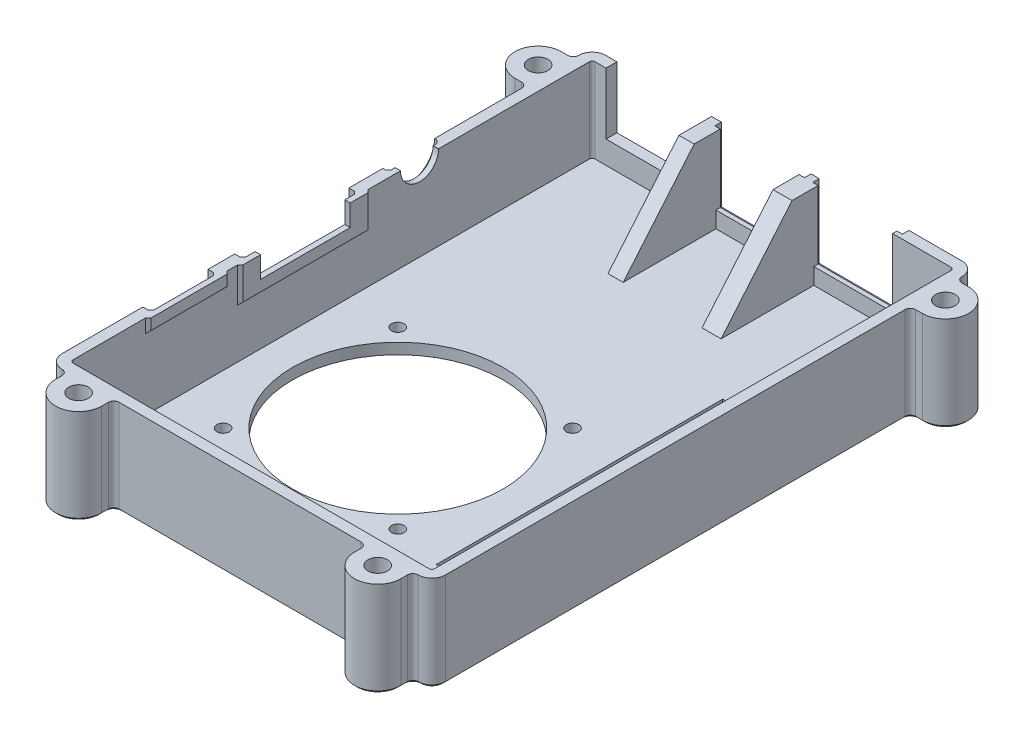
SolidWorks part; units mm, degrees
ref_plane "Front Plane" through (0, 0, 0) normal (0, 0, 1) x (1, 0, 0)
ref_plane "Top Plane" through (0, 0, 0) normal (0, 1, 0) x (1, 0, 0)
ref_plane "Right Plane" through (0, 0, 0) normal (1, 0, 0) x (0, 0, -1)
sketch "Sketch2" plane through (0, 0, 0) normal (0, 1, 0) x (1, 0, 0)
  line L1 (2.5, 0) -> (68, 0)
  line L2 (0, 2.5) -> (0, 97.5)
  line L3 (2.5, 100) -> (68, 100)
  line L4 (70.5, 2.5) -> (70.5, 97.5)
  arc A0 (0, 2.5) -> (2.5, 0) centre (2.5, 2.5) ccw
  arc A1 (68, 0) -> (70.5, 2.5) centre (68, 2.5) ccw
  arc A2 (70.5, 97.5) -> (68, 100) centre (68, 97.5) ccw
  arc A3 (2.5, 100) -> (0, 97.5) centre (2.5, 97.5) ccw
  point P7 (0, 0)
  point P10 (70.5, 0)
  point P13 (70.5, 100)
  point P16 (0, 100)
  dimension "D3" = 2.5
  dimension "D1" = 70.5
  dimension "D2" = 100
extrude "Base" add sketch "Sketch2" along normal blind 17.5
shell "Shell" thickness 2 removed face at (35.25, 17.5, -50)
sketch "Sketch14" plane through (0, 0, 0) normal (0, -1, 0) x (1, 0, 0)
  line L0 (35.25, 0) -> (35.25, -100) construction
  line L2 (68, -100) -> (2.5, -100) construction
  line L3 (-2.2, -88) -> (0, -88)
  line L4 (0, -97.5) -> (0, -2.5) construction
  line L5 (0, -88) -> (0, -96.5)
  line L6 (0, -96.5) -> (-2.2, -96.5)
  line L7 (3.5, 2.2) -> (3.5, 0)
  line L8 (2.5, 0) -> (68, 0) construction
  line L9 (3.5, 0) -> (12, 0)
  line L10 (12, 0) -> (12, 2.2)
  line L11 (72.7, -88) -> (70.5, -88)
  line L12 (70.5, -96.5) -> (72.7, -96.5)
  line L13 (70.5, -88) -> (70.5, -96.5)
  line L14 (58.5, 0) -> (58.5, 2.2)
  line L15 (67, 0) -> (58.5, 0)
  line L16 (67, 2.2) -> (67, 0)
  line L17 (2.5, 0) -> (68, 0) construction
  arc A0 (-2.2, -88) -> (-2.2, -96.5) centre (-2.2, -92.25) ccw
  arc A1 (3.5, 2.2) -> (12, 2.2) centre (7.75, 2.2) cw
  arc A2 (72.7, -88) -> (72.7, -96.5) centre (72.7, -92.25) cw
  arc A3 (67, 2.2) -> (58.5, 2.2) centre (62.75, 2.2) ccw
  dimension "D1" = 2.2
  dimension "D2" = 8.5
  dimension "D3" = 3.5
  dimension "D4" = 3.5
extrude "Clamps" add sketch "Sketch14" against normal up to surface (17.5 mm away) up to face at (35.25, 17.5, -50)
fillet "Clamp Fillets" radius 1 8 edges at (58.5, 8.75, 0) (67, 8.75, 0) (12, 8.75, 0) (3.5, 8.75, 0) (0, 8.75, -96.5) (0, 8.75, -88) (70.5, 8.75, -88) (70.5, 8.75, -96.5)
sketch "Sketch20" plane through (0, 0, 0) normal (0, -1, 0) x (1, 0, 0)
  circle A0 centre (7.75, 2.2) radius 1.8
  circle A1 centre (62.75, 2.2) radius 1.8
  circle A2 centre (72.7, -92.25) radius 1.8
  circle A3 centre (-2.2, -92.25) radius 1.8
  arc A4 (12, 2.2) -> (3.5, 2.2) centre (7.75, 2.2) ccw construction
  arc A5 (67, 2.2) -> (58.5, 2.2) centre (62.75, 2.2) ccw construction
  arc A6 (-2.2, -88) -> (-2.2, -96.5) centre (-2.2, -92.25) ccw construction
  arc A7 (72.7, -96.5) -> (72.7, -88) centre (72.7, -92.25) ccw construction
  dimension "D1" = 3.6
extrude "Clamp Holes" cut sketch "Sketch20" against normal through all
sketch "Sketch21" plane through (0, 0, 0) normal (0, -1, 0) x (1, 0, 0)
  circle A0 centre (7.75, 2.2) radius 2.9
  circle A1 centre (62.75, 2.2) radius 2.9
  circle A2 centre (72.7, -92.25) radius 2.9
  circle A3 centre (-2.2, -92.25) radius 2.9
  circle A4 centre (-2.2, -92.25) radius 1.8 construction
  circle A5 centre (7.75, 2.2) radius 1.8 construction
  circle A6 centre (62.75, 2.2) radius 1.8 construction
  circle A7 centre (72.7, -92.25) radius 1.8 construction
  dimension "D1" = 5.8
extrude "Clamp Countersinks" cut sketch "Sketch21" against normal blind 3.4
chamfer "Clamp Countersink Chamfers" distance 0.3 angle 45 4 edges at (-2.2, 0, -95.15) (72.7, 0, -95.15) (62.75, 0, -0.7) (7.75, 0, -0.7)
sketch "Sketch24" plane through (0, 0, -100) normal (0, 0, -1) x (-1, 0, 0)
  line L0 (-68, 17.5) -> (-2.5, 17.5) construction
  line L1 (-57.25, 17.5) -> (-42.75, 17.5)
  line L2 (-57.25, 17.5) -> (-57.25, 5)
  line L3 (-57.25, 5) -> (-42.75, 5)
  line L4 (-42.75, 17.5) -> (-42.75, 5)
  line L6 (0, 17.5) -> (0, 0) construction
  line L7 (-39.25, 17.5) -> (-24.75, 17.5)
  line L8 (-39.25, 17.5) -> (-39.25, 5)
  line L9 (-39.25, 5) -> (-24.75, 5)
  line L10 (-24.75, 17.5) -> (-24.75, 5)
  dimension "D1" = 14.5
  dimension "D2" = 24.75
  dimension "D3" = 42.75
  dimension "D4" = 12.5
extrude "USB Cutout" cut sketch "Sketch24" against normal blind 18.25
sketch "Sketch25" plane through (0, 0, -100) normal (0, 0, -1) x (-1, 0, 0)
  line L0 (-42.75, 17.5) -> (-39.25, 17.5) construction
  line L1 (-41.75, 17.5) -> (-58.25, 17.5)
  line L2 (-41.75, 17.5) -> (-41.75, 4)
  line L3 (-41.75, 4) -> (-58.25, 4)
  line L4 (-58.25, 17.5) -> (-58.25, 4)
  line L6 (-24.75, 17.5) -> (-2.5, 17.5) construction
  line L7 (-23.75, 17.5) -> (-40.25, 17.5)
  line L8 (-23.75, 17.5) -> (-23.75, 4)
  line L9 (-23.75, 4) -> (-40.25, 4)
  line L10 (-40.25, 17.5) -> (-40.25, 4)
  line L12 (-57.25, 17.5) -> (-57.25, 5) construction
  line L13 (-42.75, 5) -> (-42.75, 17.5) construction
  line L14 (-39.25, 17.5) -> (-39.25, 5) construction
  line L15 (-24.75, 5) -> (-24.75, 17.5) construction
  point P18 (-57.25, 11.25)
  dimension "D1" = 1
  dimension "D2" = 1
  dimension "D3" = 1
  dimension "D4" = 1
  dimension "D5" = 13.5
extrude "USB Approach" cut sketch "Sketch25" against normal blind 1.2
sketch "Sketch26" plane through (42.75, 0, 0) normal (1, 0, 0) x (0, 0, -1)
  line L0 (98, 2) -> (98, 17.5)
  line L1 (98, 17.5) -> (94, 17.5)
  line L2 (98, 2) -> (80.95, 2)
  line L3 (80.95, 2) -> (94, 17.5)
  line L4 (100, 4) -> (100, 17.5) construction
  line L5 (100, 4) -> (100, 17.5) construction
  dimension "D1" = 6
  dimension "D2" = 19.05
extrude "USB Inner Support" add sketch "Sketch26" against normal up to surface (3.5 mm away) up to face at (39.25, 11.25, -98.4)
sketch "Sketch27" plane through (24.75, 0, 0) normal (1, 0, 0) x (0, 0, -1)
  line L0 (98, 2) -> (98, 17.5)
  line L1 (98, 17.5) -> (94, 17.5)
  line L2 (98, 2) -> (80.95, 2)
  line L3 (80.95, 2) -> (94, 17.5)
  line L4 (100, 4) -> (100, 17.5) construction
  line L5 (100, 4) -> (100, 17.5) construction
  dimension "D1" = 6
  dimension "D2" = 19.05
extrude "USB Outer Support" add sketch "Sketch27" against normal blind 2.8
sketch "Sketch28" plane through (0, 0, -100) normal (0, 0, -1) x (-1, 0, 0)
  line L0 (-23.75, 17.5) -> (-2.5, 17.5) construction
  line L1 (-21.95, 17.5) -> (-4.55, 17.5)
  line L2 (-21.95, 17.5) -> (-21.95, 6.2)
  line L3 (-21.95, 6.2) -> (-4.55, 6.2)
  line L4 (-4.55, 17.5) -> (-4.55, 6.2)
  line L5 (0, 17.5) -> (0, 0) construction
  dimension "D1" = 17.4
  dimension "D2" = 4.55
  dimension "D3" = 11.3
extrude "RJ45 Cutout" cut sketch "Sketch28" against normal blind 22.7
sketch "Sketch29" plane through (2, 0, 0) normal (1, 0, 0) x (0, 0, -1)
  line L0 (97.5, 17.5) -> (2.5, 17.5) construction
  line L1 (15.85, 17.5) -> (30.85, 17.5)
  line L2 (15.85, 17.5) -> (15.85, 15)
  line L3 (15.85, 15) -> (30.85, 15)
  line L4 (30.85, 17.5) -> (30.85, 15)
  line L5 (0, 17.5) -> (0, 0) construction
  line L6 (32.75, 17.5) -> (56.75, 17.5)
  line L7 (32.75, 17.5) -> (32.75, 11.07)
  line L8 (32.75, 11.07) -> (56.75, 11.07)
  line L9 (56.75, 17.5) -> (56.75, 11.07)
  dimension "D1" = 24
  dimension "D2" = 15
  dimension "D3" = 15.85
  dimension "D4" = 32.75
  dimension "D5" = 2.5
  dimension "D6" = 6.43
extrude "HDMI Support" add sketch "Sketch29" along normal blind 0.5
chamfer "HDMI Support Chamfer" distance 0.5 angle 45 6 edges at (2.5, 14.285, -56.75) (2.5, 11.07, -44.75) (2.5, 14.285, -32.75) (2.5, 16.25, -30.85) (2.5, 15, -23.35) (2.5, 16.25, -15.85)
sketch "Sketch30" plane through (0, 0, 0) normal (-1, 0, 0) x (0, 0, 1)
  line L0 (-87, 17.5) -> (-2.5, 17.5) construction
  line L1 (-34.25, 17.5) -> (-55.25, 17.5)
  line L2 (-34.25, 17.5) -> (-34.25, 11.57)
  line L3 (-34.25, 11.57) -> (-55.25, 11.57)
  line L4 (-55.25, 17.5) -> (-55.25, 11.57)
  line L5 (0, 17.5) -> (0, 0) construction
  line L6 (-29.35, 17.5) -> (-17.35, 17.5)
  line L7 (-29.35, 17.5) -> (-29.35, 15.5)
  line L8 (-29.35, 15.5) -> (-17.35, 15.5)
  line L9 (-17.35, 17.5) -> (-17.35, 15.5)
  dimension "D1" = 12
  dimension "D2" = 21
  dimension "D3" = 17.35
  dimension "D4" = 34.25
  dimension "D5" = 5.93
  dimension "D6" = 2
extrude "HDMI Approach" cut sketch "Sketch30" against normal blind 1.5
sketch "Sketch31" plane through (1.5, 0, 0) normal (-1, 0, 0) x (0, 0, 1)
  line L0 (-34.25, 17.5) -> (-55.25, 17.5) construction
  line L1 (-53, 17.5) -> (-36.5, 17.5)
  line L2 (-53, 17.5) -> (-53, 13.57)
  line L3 (-53, 13.57) -> (-36.5, 13.57)
  line L4 (-36.5, 17.5) -> (-36.5, 13.57)
  line L5 (-55.25, 17.5) -> (-55.25, 11.57) construction
  line L6 (-34.25, 11.57) -> (-34.25, 17.5) construction
  line L7 (-55.25, 11.57) -> (-34.25, 11.57) construction
  dimension "D1" = 2.25
  dimension "D2" = 2.25
  dimension "D3" = 2
extrude "HDMI Cutout" cut sketch "Sketch31" against normal blind 1
chamfer "HDMI Approach Chamfer" distance 0.5 angle 45 6 edges at (1.5, 16.5, -17.35) (1.5, 15.5, -23.35) (1.5, 16.5, -29.35) (1.5, 14.535, -34.25) (1.5, 11.57, -44.75) (1.5, 14.535, -55.25)
sketch "Sketch32" plane through (0, 0, 0) normal (-1, 0, 0) x (0, 0, 1)
  line L0 (-87, 17.5) -> (-55.25, 17.5) construction
  line L1 (0, 17.5) -> (0, 0) construction
  circle A0 centre (-66.25, 17.5) radius 3.5
  dimension "D1" = 7
  dimension "D2" = 66.25
extrude "Audio Cutout" cut sketch "Sketch32" against normal blind 2
sketch "Sketch33" plane through (0, 0, 0) normal (-1, 0, 0) x (0, 0, 1)
  circle A0 centre (-66.25, 17.5) radius 4.75
  arc A1 (-69.75, 17.5) -> (-62.75, 17.5) centre (-66.25, 17.5) ccw construction
  dimension "D1" = 9.5
extrude "Audio Approach" cut sketch "Sketch33" against normal blind 1
chamfer "Audio Approach Chamfer" distance 0.5 angle 45 1 edges at (1, 12.75, -66.25)
sketch "Sketch34" plane through (0, 0, 0) normal (0, -1, 0) x (1, 0, 0)
  line L0 (70.5, -2.5) -> (70.5, -87) construction
  line L1 (52.5, -18.8) -> (58.5, -18.8)
  line L2 (52.5, -18.8) -> (52.5, -71.5)
  line L3 (52.5, -71.5) -> (58.5, -71.5)
  line L4 (58.5, -18.8) -> (58.5, -71.5)
  line L5 (13, 0) -> (57.5, 0) construction
  point P6 (55.5, -18.8)
  dimension "D1" = 6
  dimension "D2" = 52.7
  dimension "D3" = 12
  dimension "D4" = 18.8
extrude "Header Cutout" cut sketch "Sketch34" against normal blind 2
sketch "Sketch35" plane through (0, 0, 0) normal (0, -1, 0) x (1, 0, 0)
  line L0 (55.5, -18.8) -> (55.5, -71.5) construction
  line L1 (58.5, -18.8) -> (52.5, -18.8) construction
  line L2 (52.5, -71.5) -> (58.5, -71.5) construction
  line L3 (52.5, -45.15) -> (58.5, -45.15) construction
  line L4 (52.5, -18.8) -> (52.5, -71.5) construction
  line L5 (58.5, -71.5) -> (58.5, -18.8) construction
  line L6 (56, -18.8) -> (55, -18.8)
  line L7 (55, -18.8) -> (55, -19.8)
  line L8 (55, -19.8) -> (53.5, -19.8)
  line L9 (53.5, -19.8) -> (53.5, -24.7625)
  line L10 (53.5, -24.7625) -> (52.5, -24.7625)
  line L11 (52.5, -24.7625) -> (52.5, -25.7625)
  line L12 (52.5, -25.7625) -> (53.5, -25.7625)
  line L13 (53.5, -25.7625) -> (53.5, -37.6875)
  line L14 (53.5, -37.6875) -> (52.5, -37.6875)
  line L15 (52.5, -37.6875) -> (52.5, -38.6875)
  line L16 (52.5, -38.6875) -> (53.5, -38.6875)
  line L17 (53.5, -38.6875) -> (53.5, -43.65)
  line L18 (53.5, -43.65) -> (55, -43.65)
  line L19 (55, -43.65) -> (55, -44.65)
  line L20 (55, -44.65) -> (52.5, -44.65)
  line L21 (52.5, -44.65) -> (52.5, -45.65)
  line L22 (56, -71.5) -> (55, -71.5)
  line L23 (55, -45.65) -> (52.5, -45.65)
  line L24 (55, -46.65) -> (55, -45.65)
  line L25 (53.5, -46.65) -> (55, -46.65)
  line L26 (53.5, -51.6125) -> (53.5, -46.65)
  line L27 (52.5, -51.6125) -> (53.5, -51.6125)
  line L28 (52.5, -52.6125) -> (52.5, -51.6125)
  line L29 (53.5, -52.6125) -> (52.5, -52.6125)
  line L30 (53.5, -64.5375) -> (53.5, -52.6125)
  line L31 (52.5, -64.5375) -> (53.5, -64.5375)
  line L32 (52.5, -65.5375) -> (52.5, -64.5375)
  line L33 (53.5, -65.5375) -> (52.5, -65.5375)
  line L34 (53.5, -70.5) -> (53.5, -65.5375)
  line L35 (55, -70.5) -> (53.5, -70.5)
  line L36 (55, -71.5) -> (55, -70.5)
  line L37 (56, -71.5) -> (56, -70.5)
  line L38 (56, -70.5) -> (57.5, -70.5)
  line L39 (57.5, -70.5) -> (57.5, -65.5375)
  line L40 (57.5, -65.5375) -> (58.5, -65.5375)
  line L41 (58.5, -65.5375) -> (58.5, -64.5375)
  line L42 (58.5, -64.5375) -> (57.5, -64.5375)
  line L43 (57.5, -64.5375) -> (57.5, -52.6125)
  line L44 (57.5, -52.6125) -> (58.5, -52.6125)
  line L45 (58.5, -52.6125) -> (58.5, -51.6125)
  line L46 (58.5, -51.6125) -> (57.5, -51.6125)
  line L47 (57.5, -51.6125) -> (57.5, -46.65)
  line L48 (57.5, -46.65) -> (56, -46.65)
  line L49 (56, -46.65) -> (56, -45.65)
  line L50 (56, -45.65) -> (58.5, -45.65)
  line L51 (58.5, -44.65) -> (58.5, -45.65)
  line L52 (56, -44.65) -> (58.5, -44.65)
  line L53 (56, -43.65) -> (56, -44.65)
  line L54 (57.5, -43.65) -> (56, -43.65)
  line L55 (57.5, -38.6875) -> (57.5, -43.65)
  line L56 (58.5, -38.6875) -> (57.5, -38.6875)
  line L57 (58.5, -37.6875) -> (58.5, -38.6875)
  line L58 (57.5, -37.6875) -> (58.5, -37.6875)
  line L59 (57.5, -25.7625) -> (57.5, -37.6875)
  line L60 (58.5, -25.7625) -> (57.5, -25.7625)
  line L61 (58.5, -24.7625) -> (58.5, -25.7625)
  line L62 (57.5, -24.7625) -> (58.5, -24.7625)
  line L63 (57.5, -19.8) -> (57.5, -24.7625)
  line L64 (56, -19.8) -> (57.5, -19.8)
  line L65 (56, -18.8) -> (56, -19.8)
  dimension "D1" = 0.5
  dimension "D2" = 1
  dimension "D3" = 1.5
  dimension "D4" = 11.925
extrude "Header Cover" add sketch "Sketch35" against normal blind 1
chamfer "Shell Chamfer" distance 0.5 angle 45 44 edges at (53.75, 0, -71.5) (52.5, 0, -68.5187) (52.5, 0, -58.575) (52.5, 0, -48.6313) (52.5, 0, -41.6688) (52.5, 0, -31.725) (52.5, 0, -21.7813) (53.75, 0, -18.8) (57.25, 0, -18.8) (58.5, 0, -21.7813) (58.5, 0, -31.725) (58.5, 0, -41.6688) (58.5, 0, -48.6313) (58.5, 0, -58.575) (58.5, 0, -68.5187) (57.25, 0, -71.5) (69.7678, 0, -99.2678) (70.7929, 0, -96.7929) (72.1, 0, -96.5) (76.95, 0, -92.25) (72.1, 0, -88) (70.7929, 0, -87.7071) (70.5, 0, -44.75) (35.25, 0, -100) (0.7322, 0, -99.2678) (-0.2929, 0, -96.7929) (-1.6, 0, -96.5) (-6.45, 0, -92.25) (-1.6, 0, -88) (0, 0, -44.75) (69.7678, 0, -0.7322) (67.2929, 0, 0.2929) (67, 0, 1.6) (62.75, 0, 6.45) (58.5, 0, 1.6) (58.2071, 0, 0.2929) (0.7322, 0, -0.7322) (3.5, 0, 1.6) (7.75, 0, 6.45) (12, 0, 1.6) (12.2929, 0, 0.2929) (35.25, 0, 0) (-0.2929, 0, -87.7071) (3.2071, 0, 0.2929)
sketch "Sketch39" plane through (0, 0, 0) normal (0, -1, 0) x (1, 0, 0)
  line L0 (0, -87) -> (0, -2.5) construction
  line L1 (13, 0) -> (57.5, 0) construction
  line L2 (27.25, -37) -> (49.97, -37) construction
  line L3 (27.25, -14.28) -> (27.25, -56.37) construction
  line L4 (27.25, -37) -> (43.3155, -20.9345) construction
  circle A0 centre (27.25, -37) radius 22.72 construction
  circle A1 centre (27.25, -37) radius 19.37
  circle A2 centre (43.3155, -20.9345) radius 1.15
  circle A3 centre (43.3155, -53.0655) radius 1.15
  circle A4 centre (11.1845, -53.0655) radius 1.15
  circle A5 centre (11.1845, -20.9345) radius 1.15
  dimension "D3" = 45.44
  dimension "D4" = 38.74
  dimension "D6" = 2.3
  dimension "D1" = 27.25
  dimension "D2" = 37
  dimension "D5" = 45
extrude "Fan Mount" cut sketch "Sketch39" against normal up to surface (2 mm away) up to face at (55.5, 2, -45.15)
